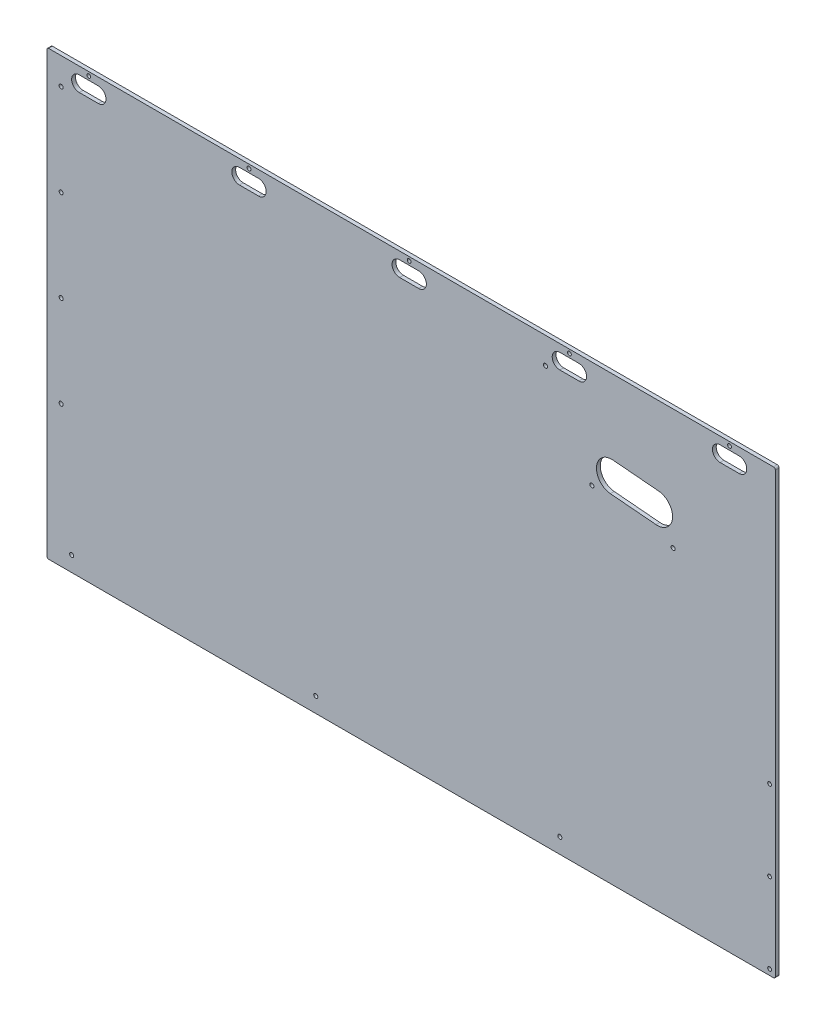
SolidWorks part; units mm, degrees
material "PC High Viscosity"
ref_plane "Front Plane" through (0, 0, 0) normal (0, 0, 1) x (1, 0, 0)
ref_plane "Top Plane" through (0, 0, 0) normal (0, 1, 0) x (1, 0, 0)
ref_plane "Right Plane" through (0, 0, 0) normal (1, 0, 0) x (0, 0, -1)
sketch "Sketch1" plane through (0, 0, 0) normal (0, 0, 1) x (1, 0, 0)
  line L1 (-606.425, -368.3) -> (606.425, -368.3)
  line L2 (-606.425, -368.3) -> (-606.425, 368.3)
  line L3 (-606.425, 368.3) -> (606.425, 368.3)
  line L4 (606.425, -368.3) -> (606.425, 368.3)
  line L5 (-606.425, -368.3) -> (606.425, 368.3) construction
  line L6 (-606.425, 368.3) -> (606.425, -368.3) construction
  point P0 (0, 0)
  dimension "D1" = 1212.85
  dimension "D2" = 736.6
extrude "Boss-Extrude1" add sketch "Sketch1" along normal blind 6.35
hole_wizard "H (0.266) Diameter Hole1" positions "Sketch3" profile "Sketch4" hole size "H" standard "ANSI Inch" end condition through all
sketch "Sketch3" plane through (0, 0, 6.35) normal (0, 0, 1) x (1, 0, 0)
  line L0 (-565.15, -342.9) -> (-158.75, -342.9) construction
  line L1 (-158.75, -342.9) -> (247.65, -342.9) construction
  line L3 (-606.425, -368.3) -> (606.425, -368.3) construction
  line L4 (-606.425, 368.3) -> (-606.425, -368.3) construction
  point P0 (-565.15, -342.9)
  point P2 (-158.75, -342.9)
  point P4 (247.65, -342.9)
  dimension "D1" = 25.4
  dimension "D2" = 406.4
  dimension "D3" = 41.275
sketch "Sketch4" plane through (-565.15, -342.9, 6.35) normal (1, 0, 0) x (0, -1, 0)
  line L0 (0, 0) -> (0, 6.35)
  line L1 (0, 6.35) -> (3.3782, 6.35)
  line L2 (3.3782, 6.35) -> (3.3782, 0)
  line L5 (3.3782, 0) -> (0, 0)
  line L11 (0, -6.35) -> (0, 107.95) construction
  dimension "Thru Hole Dia." = 6.7564
  dimension "Thru Hole Depth" = 6.35
hole_wizard "H (0.266) Diameter Hole2" positions "Sketch5" profile "Sketch6" hole size "H" standard "ANSI Inch" end condition through all
sketch "Sketch5" plane through (0, 0, 6.35) normal (0, 0, 1) x (1, 0, 0)
  line L0 (-582.6125, 323.596) -> (-582.6125, 171.196) construction
  line L1 (-582.6125, 171.196) -> (-582.6125, 18.796) construction
  line L2 (-582.6125, 18.796) -> (-582.6125, -133.604) construction
  line L5 (606.425, 368.3) -> (-606.425, 368.3) construction
  line L13 (-606.425, 368.3) -> (-606.425, -368.3) construction
  point P0 (-582.6125, 323.596)
  point P2 (-582.6125, 171.196)
  point P4 (-582.6125, 18.796)
  point P6 (-582.6125, -133.604)
  dimension "D1" = 23.8125
  dimension "D2" = 44.704
  dimension "D3" = 152.4
sketch "Sketch6" plane through (-582.6125, 323.596, 6.35) normal (1, 0, 0) x (0, -1, 0)
  line L0 (0, 0) -> (0, 6.35)
  line L1 (0, 6.35) -> (3.3782, 6.35)
  line L2 (3.3782, 6.35) -> (3.3782, 0)
  line L5 (3.3782, 0) -> (0, 0)
  line L11 (0, -6.35) -> (0, 107.95) construction
  dimension "Thru Hole Dia." = 6.7564
  dimension "Thru Hole Depth" = 6.35
hole_wizard "H (0.266) Diameter Hole3" positions "Sketch8" profile "Sketch9" hole size "H" standard "ANSI Inch" end condition through all
sketch "Sketch8" plane through (0, 0, 6.35) normal (0, 0, 1) x (1, 0, 0)
  line L5 (223.7708, 324.3059) -> (301.0598, 190.4374) construction
  line L6 (301.0598, 190.4374) -> (436.1577, 167.7114) construction
  line L7 (606.425, 368.3) -> (-606.425, 368.3) construction
  line L8 (606.425, -368.3) -> (606.425, 368.3) construction
  point P0 (223.7708, 324.3059)
  point P3 (223.7708, 324.3059)
  point P9 (436.1577, 167.7114)
  point P32 (301.0598, 190.4374)
  dimension "D1" = 43.9941
  dimension "D2" = 382.6542
  dimension "D3" = 154.578
  dimension "D4" = 136.9961
  dimension "D5" = 60
  dimension "D6" = 9.549
sketch "Sketch9" plane through (223.7708, 324.3059, 6.35) normal (1, 0, 0) x (0, -1, 0)
  line L0 (0, 0) -> (0, 6.35)
  line L1 (0, 6.35) -> (3.3782, 6.35)
  line L2 (3.3782, 6.35) -> (3.3782, 0)
  line L5 (3.3782, 0) -> (0, 0)
  line L11 (0, -6.35) -> (0, 107.95) construction
  dimension "Thru Hole Dia." = 6.7564
  dimension "Thru Hole Depth" = 6.35
sketch "Sketch12" plane through (0, 0, 6.35) normal (0, 0, 1) x (1, 0, 0)
  line L0 (-606.425, 361.95) -> (-536.575, 361.95) construction
  line L1 (-606.425, 368.3) -> (-606.425, -368.3) construction
  line L2 (606.425, 368.3) -> (-606.425, 368.3) construction
  line L3 (-552.45, 342.9) -> (-520.7, 342.9) construction
  line L4 (-552.45, 355.6) -> (-520.7, 355.6)
  line L5 (-552.45, 330.2) -> (-520.7, 330.2)
  circle A0 centre (-536.575, 361.95) radius 3.175
  arc A1 (-552.45, 355.6) -> (-552.45, 330.2) centre (-552.45, 342.9) ccw
  arc A2 (-520.7, 330.2) -> (-520.7, 355.6) centre (-520.7, 342.9) ccw
  point P9 (-536.575, 342.9)
  dimension "D3" = 6.35
  dimension "D5" = 12.7
  dimension "D1" = 69.85
  dimension "D2" = 6.35
  dimension "D4" = 31.75
  dimension "D6" = 19.05
extrude "Cut-Extrude4" cut sketch "Sketch12" against normal through all
pattern_linear "LPattern1" count 5 spacing 266.7 along (1, 0, 0) of "Cut-Extrude4"
fillet "Fillet2" radius 3.175 4 edges at (606.425, 368.3, 3.175) (606.425, -368.3, 3.175) (-606.425, -368.3, 3.175) (-606.425, 368.3, 3.175)
sketch "Sketch14" plane through (0, 0, 6.35) normal (0, 0, 1) x (1, 0, 0)
  line L0 (603.25, 368.3) -> (-603.25, 368.3) construction
  line L1 (371.9822, 215.9) -> (371.9822, 368.3) construction
  line L2 (334.0272, 219.2206) -> (409.9372, 212.5794) construction
  line L3 (336.2409, 244.524) -> (412.1509, 237.8827)
  line L4 (331.8134, 193.9173) -> (407.7234, 187.276)
  line L6 (606.425, -365.125) -> (606.425, 365.125) construction
  arc A1 (336.2409, 244.524) -> (331.8134, 193.9173) centre (334.0272, 219.2206) ccw
  arc A2 (407.7234, 187.276) -> (412.1509, 237.8827) centre (409.9372, 212.5794) ccw
  point P2 (371.9822, 215.9)
  dimension "D1" = 25.4
  dimension "D2" = 76.2
  dimension "D3" = 5
  dimension "D4" = 152.4
  dimension "D5" = 234.4428
extrude "Cut-Extrude5" cut sketch "Sketch14" against normal through all
hole_wizard "1/4 (0.25) Diameter Hole1" positions "Sketch15" profile "Sketch16" hole size "1/4" standard "ANSI Inch" end condition through all
sketch "Sketch15" plane through (0, 0, 6.35) normal (0, 0, 1) x (1, 0, 0)
  line L0 (-603.25, -368.3) -> (603.25, -368.3) construction
  line L1 (606.425, -365.125) -> (606.425, 365.125) construction
  point P0 (596.9, -358.775)
  point P2 (596.9, -225.425)
  point P4 (596.9, -92.075)
  dimension "D1" = 9.525
  dimension "D2" = 133.35
  dimension "D3" = 133.35
  dimension "D4" = 9.525
sketch "Sketch16" plane through (596.9, -358.775, 6.35) normal (1, 0, 0) x (0, -1, 0)
  line L0 (0, 0) -> (0, 6.35)
  line L1 (0, 6.35) -> (3.175, 6.35)
  line L2 (3.175, 6.35) -> (3.175, 0)
  line L5 (3.175, 0) -> (0, 0)
  line L11 (0, -6.35) -> (0, 107.95) construction
  dimension "Thru Hole Dia." = 6.35
  dimension "Thru Hole Depth" = 6.35
